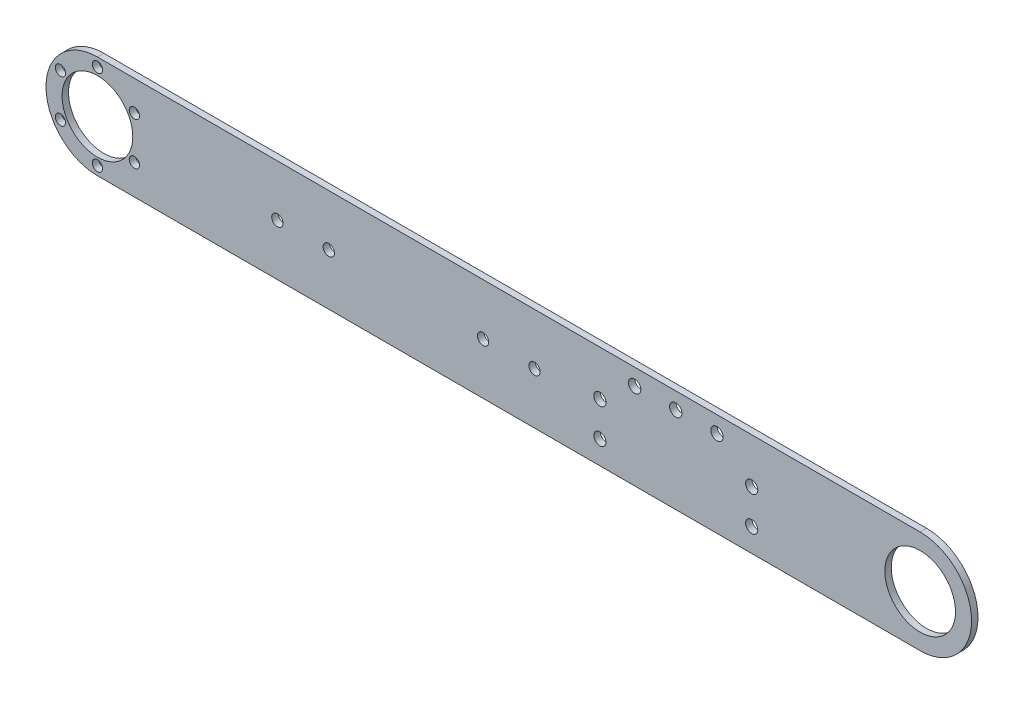
SolidWorks part; units mm, degrees
ref_plane "Front Plane" through (0, 0, 0) normal (0, 0, 1) x (1, 0, 0)
ref_plane "Top Plane" through (0, 0, 0) normal (0, 1, 0) x (1, 0, 0)
ref_plane "Right Plane" through (0, 0, 0) normal (1, 0, 0) x (0, 0, -1)
sketch "Sketch1" plane through (0, 0, 0) normal (0, 0, 1) x (1, 0, 0)
  line L1 (0, 0) -> (406.4, 0)
  line L3 (0, 50.8) -> (406.4, 50.8)
  arc A0 (0, 50.8) -> (0, 0) centre (0, 25.4) ccw
  arc A1 (406.4, 0) -> (406.4, 50.8) centre (406.4, 25.4) ccw
  dimension "D1" = 406.4
  dimension "D2" = 50.8
extrude "Boss-Extrude1" add sketch "Sketch1" along normal blind 3.175
sketch "Sketch2" plane through (0, 0, 3.175) normal (0, 0, 1) x (1, 0, 0)
  circle A0 centre (0, 25.4) radius 17.4625
  arc A1 (0, 50.8) -> (0, 0) centre (0, 25.4) ccw construction
  circle A3 centre (406.4, 25.4) radius 17.4625
  arc A5 (406.4, 0) -> (406.4, 50.8) centre (406.4, 25.4) ccw construction
  dimension "D1" = 34.925
  dimension "D2" = 34.925
extrude "Cut-Extrude1" cut sketch "Sketch2" against normal through all
sketch "Sketch4" plane through (0, 0, 3.175) normal (0, 0, 1) x (1, 0, 0)
  line L0 (0, 25.4) -> (381, 25.4) construction
  circle A0 centre (88.9, 25.4) radius 2.794
  circle A1 centre (0, 25.4) radius 17.4625 construction
  circle A2 centre (114.3, 25.4) radius 2.794
  circle A3 centre (190.5, 25.4) radius 2.794
  circle A4 centre (215.9, 25.4) radius 2.794
  point P0 (0, 46.482)
  point P4 (0, 25.4)
  point P5 (18.2575, 35.941)
  point P7 (18.2575, 14.859)
  point P8 (0, 4.318)
  point P9 (-18.2575, 14.859)
  point P10 (-18.2575, 35.941)
  point P11 (0, 25.4)
  dimension "D3" = 5.588
  dimension "D4" = 88.9
  dimension "D5" = 25.4
  dimension "D6" = 5.588
  dimension "D7" = 25.4
  dimension "D8" = 76.2
  dimension "D1" = 21.082
  dimension "D2" = 6
hole_wizard "#10 Clearance Hole1" positions "3DSketch2" profile "Sketch5" hole size "#10" standard "ANSI Inch" end condition through all
sketch3d "3DSketch2"
  point P0 (18.2575, 35.941, 3.175)
  point P3 (18.2575, 14.859, 3.175)
  point P6 (0, 4.318, 3.175)
  point P9 (-18.2575, 14.859, 3.175)
  point P12 (-18.2575, 35.941, 3.175)
  point P15 (0, 46.482, 3.175)
sketch "Sketch5" plane through (18.2575, 35.941, 3.175) normal (1, 0, 0) x (0, -1, 0)
  line L0 (0, 0) -> (0, 3.175)
  line L1 (0, 3.175) -> (2.5527, 3.175)
  line L2 (2.5527, 3.175) -> (2.5527, 0)
  line L5 (2.5527, 0) -> (0, 0)
  line L11 (0, -6.35) -> (0, 107.95) construction
  dimension "Thru Hole Dia." = 5.1054
  dimension "Thru Hole Depth" = 3.175
ref_axis "Axis1" through (203.2, 50.8, 0) along (0, -0.9981, 0.0624)
ref_plane "Plane1" through (203.2, 0, 0) normal (1, 0, 0) x (0, 0, -1)
extrude "Cut-Extrude2" cut sketch "Sketch4" against normal through all
sketch "Sketch7" plane through (0, 0, 3.175) normal (0, 0, 1) x (1, 0, 0)
  line L0 (334.2879, 42.672) -> (260.3158, 42.672) construction
  line L1 (406.4, 50.8) -> (0, 50.8) construction
  circle A0 centre (306.0152, 42.672) radius 3.048
  circle A1 centre (285.6952, 42.672) radius 3.048
  circle A2 centre (265.3752, 42.672) radius 3.048
  dimension "D2" = 6.096
  dimension "D3" = 20.32
  dimension "D4" = 20.32
  dimension "D1" = 8.128
extrude "Cut-Extrude3" cut sketch "Sketch7" against normal through all
sketch "Sketch8" plane through (0, 0, 3.175) normal (0, 0, 1) x (1, 0, 0)
  circle A0 centre (323.1952, 11.5433) radius 3
  circle A1 centre (323.1952, 28.5433) radius 3
  circle A2 centre (248.1952, 11.5433) radius 3
  circle A3 centre (248.1952, 28.5433) radius 3
extrude "Cut-Extrude4" cut sketch "Sketch8" against normal through all
